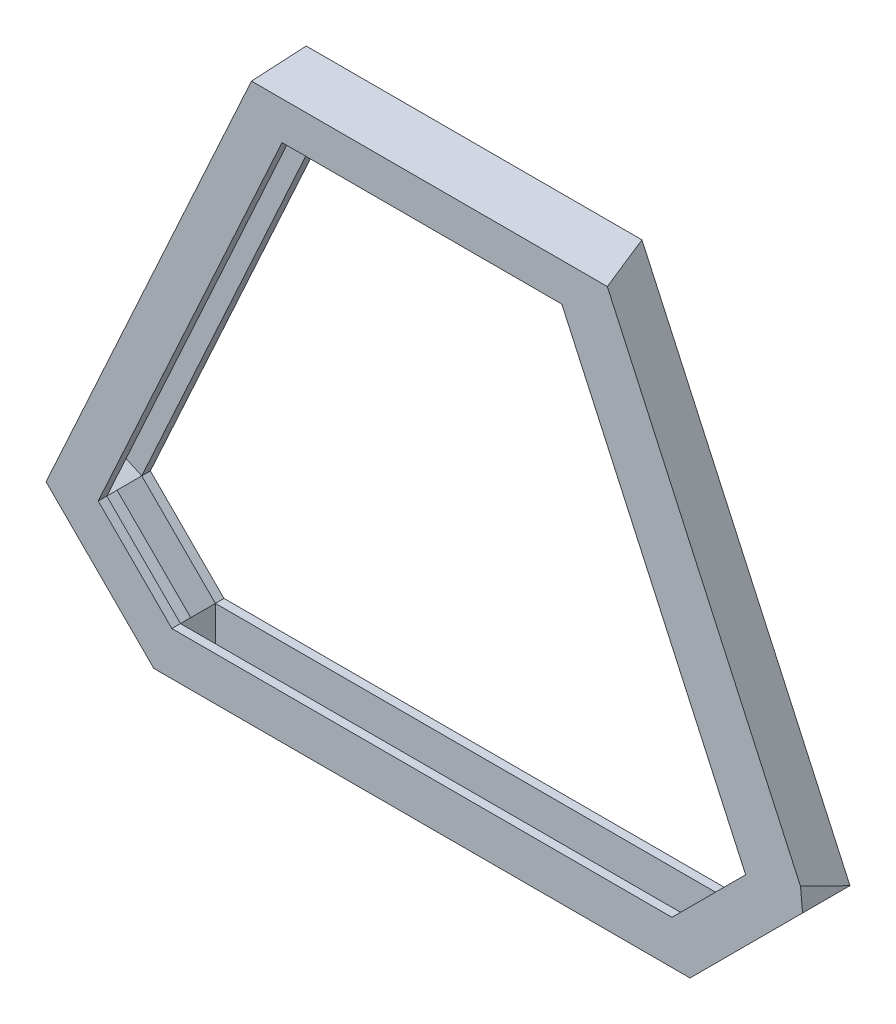
SolidWorks part; units mm, degrees
ref_plane "Front Plane" through (0, 0, 0) normal (0, 0, 1) x (1, 0, 0)
ref_plane "Top Plane" through (0, 0, 0) normal (0, 1, 0) x (1, 0, 0)
ref_plane "Right Plane" through (0, 0, 0) normal (1, 0, 0) x (0, 0, -1)
sketch "Sketch1" plane through (0, 0, 0) normal (0, 0, 1) x (1, 0, 0)
  line L0 (0, -264.5165) -> (-62.614, -327.1305)
  line L1 (-62.614, -327.1305) -> (-374.1336, -327.1305)
  line L2 (-374.1336, -327.1305) -> (-436.7476, -264.5165)
  line L3 (-436.7476, -264.5165) -> (-315.9032, 0)
  line L4 (-315.9032, 0) -> (-120.8445, 0)
  line L5 (-120.8445, 0) -> (0, -264.5165)
extrude "Boss-Extrude1" add sketch "Sketch1" along normal blind 5
sketch "Sketch2" plane through (0, 0, 5) normal (0, 0, 1) x (1, 0, 0)
  line L0 (-315.9032, 0) -> (-436.7476, -264.5165) construction
  line L1 (-436.7476, -264.5165) -> (-374.1336, -327.1305) construction
  line L2 (-374.1336, -327.1305) -> (-62.614, -327.1305) construction
  line L3 (-62.614, -327.1305) -> (0, -264.5165) construction
  line L4 (0, -264.5165) -> (-120.8445, 0) construction
  line L5 (-120.8445, 0) -> (-315.9032, 0) construction
  line L6 (-374.1336, -327.1305) -> (-370.5981, -323.595) construction
  line L7 (-436.7476, -264.5165) -> (-433.2121, -260.981) construction
  line L8 (-315.9032, 0) -> (-311.3553, -2.0777) construction
  line L9 (-436.7476, -264.5165) -> (-432.1998, -266.5942) construction
  line L10 (-315.9032, 0) -> (-315.9032, -5) construction
  line L11 (-120.8445, 0) -> (-120.8445, -5) construction
  line L12 (-120.8445, 0) -> (-125.3924, -2.0777) construction
  line L13 (0, -264.5165) -> (-4.5479, -266.5942) construction
  line L14 (-374.1336, -327.1305) -> (-374.1336, -322.1305) construction
  line L15 (-62.614, -327.1305) -> (-62.614, -322.1305) construction
  line L16 (-62.614, -327.1305) -> (-66.1495, -323.595) construction
  line L17 (0, -264.5165) -> (-3.5355, -260.981) construction
  line L18 (-433.2121, -260.981) -> (-370.5981, -323.595) construction
  line L19 (-374.1336, -322.1305) -> (-62.614, -322.1305) construction
  line L20 (-3.5355, -260.981) -> (-66.1495, -323.595) construction
  line L21 (-125.3924, -2.0777) -> (-4.5479, -266.5942) construction
  line L22 (-120.8445, -5) -> (-315.9032, -5) construction
  line L23 (-311.3553, -2.0777) -> (-432.1998, -266.5942) construction
  line L24 (-311.3553, -2.0777) -> (-292.8909, -10.5132) construction
  line L25 (-315.9032, -5) -> (-315.9032, -25.3) construction
  line L26 (-433.2121, -260.981) -> (-418.8578, -246.6267) construction
  line L27 (-432.1998, -266.5942) -> (-413.7354, -275.0297) construction
  line L28 (-374.1336, -322.1305) -> (-374.1336, -301.8305) construction
  line L29 (-370.5981, -323.595) -> (-356.2438, -309.2407) construction
  line L30 (-66.1495, -323.595) -> (-80.5038, -309.2407) construction
  line L31 (-62.614, -322.1305) -> (-62.614, -301.8305) construction
  line L32 (-4.5479, -266.5942) -> (-23.0122, -275.0297) construction
  line L33 (-3.5355, -260.981) -> (-17.8898, -246.6267) construction
  line L34 (-120.8445, -5) -> (-120.8445, -25.3) construction
  line L35 (-125.3924, -2.0777) -> (-143.8567, -10.5132) construction
  line L36 (-315.9032, -25.3) -> (-120.8445, -25.3) construction
  line L37 (-143.8567, -10.5132) -> (-23.0122, -275.0297) construction
  line L38 (-17.8898, -246.6267) -> (-80.5038, -309.2407) construction
  line L39 (-62.614, -301.8305) -> (-374.1336, -301.8305) construction
  line L40 (-356.2438, -309.2407) -> (-418.8578, -246.6267) construction
  line L41 (-413.7354, -275.0297) -> (-292.8909, -10.5132) construction
sketch "Sketch3" plane through (0, 0, 5) normal (0, 0, 1) x (1, 0, 0)
  line L7 (-137.1013, -25.3) -> (-299.6463, -25.3)
  line L8 (-143.8567, -10.5132) -> (-23.0122, -275.0297) construction
  line L9 (-413.7354, -275.0297) -> (-292.8909, -10.5132) construction
  line L10 (-315.9032, -25.3) -> (-120.8445, -25.3) construction
  line L11 (-137.1013, -25.3) -> (-30.3127, -259.0496)
  line L12 (-17.8898, -246.6267) -> (-80.5038, -309.2407) construction
  line L13 (-30.3127, -259.0496) -> (-73.0936, -301.8305)
  line L14 (-299.6463, -25.3) -> (-406.4349, -259.0496)
  line L15 (-356.2438, -309.2407) -> (-418.8578, -246.6267) construction
  line L16 (-62.614, -301.8305) -> (-374.1336, -301.8305) construction
  line L17 (-406.4349, -259.0496) -> (-363.654, -301.8305)
  line L18 (-73.0936, -301.8305) -> (-363.654, -301.8305)
extrude "Cut-Extrude1" cut sketch "Sketch3" against normal through all
sketch "Sketch4" plane through (0, 0, 5) normal (0, 0, 1) x (1, 0, 0)
  line L0 (-312.6903, -5) -> (-124.0573, -5)
  line L1 (-120.8445, -5) -> (-315.9032, -5) construction
  line L2 (-311.3553, -2.0777) -> (-432.1998, -266.5942) construction
  line L3 (-125.3924, -2.0777) -> (-4.5479, -266.5942) construction
  line L4 (-312.6903, -5) -> (-430.757, -263.4361)
  line L5 (-433.2121, -260.981) -> (-370.5981, -323.595) construction
  line L6 (-430.757, -263.4361) -> (-372.0626, -322.1305)
  line L11 (-374.1336, -322.1305) -> (-62.614, -322.1305) construction
  line L12 (-372.0626, -322.1305) -> (-64.6851, -322.1305)
  line L13 (-3.5355, -260.981) -> (-66.1495, -323.595) construction
  line L14 (-64.6851, -322.1305) -> (-5.9907, -263.4361)
  line L15 (-5.9907, -263.4361) -> (-124.0573, -5)
  line L16 (-315.9032, 0) -> (-120.8445, 0)
  line L17 (-315.9032, 0) -> (-436.7476, -264.5165)
  line L18 (-436.7476, -264.5165) -> (-374.1336, -327.1305)
  line L19 (-374.1336, -327.1305) -> (-62.614, -327.1305)
  line L20 (-62.614, -327.1305) -> (0, -264.5165)
  line L21 (0, -264.5165) -> (-120.8445, 0)
extrude "Boss-Extrude3" add sketch "Sketch4" along normal blind 20.3
sketch "Sketch5" plane through (0, 0, 5) normal (0, 0, 1) x (1, 0, 0)
  line L0 (-299.6463, -25.3) -> (-318.1107, -16.8645)
  line L1 (-312.6903, -5) -> (-430.757, -263.4361) construction
  line L2 (-299.6463, -25.3) -> (-299.6463, -5)
  line L3 (-124.0573, -5) -> (-312.6903, -5) construction
  line L4 (-137.1013, -25.3) -> (-137.1013, -5)
  line L5 (-137.1013, -25.3) -> (-118.637, -16.8645)
  line L6 (-5.9907, -263.4361) -> (-124.0573, -5) construction
  line L7 (-406.4349, -259.0496) -> (-424.8993, -250.6142)
  line L8 (-406.4349, -259.0496) -> (-420.7892, -273.4039)
  line L9 (-430.757, -263.4361) -> (-372.0626, -322.1305) construction
  line L10 (-363.654, -301.8305) -> (-378.0083, -316.1848)
  line L11 (-363.654, -301.8305) -> (-363.654, -322.1305)
  line L12 (-372.0626, -322.1305) -> (-64.6851, -322.1305) construction
  line L13 (-372.0626, -322.1305) -> (-64.6851, -322.1305) construction
  line L14 (-73.0936, -301.8305) -> (-73.0936, -322.1305)
  line L15 (-73.0936, -301.8305) -> (-58.7393, -316.1848)
  line L16 (-64.6851, -322.1305) -> (-5.9907, -263.4361) construction
  line L17 (-30.3127, -259.0496) -> (-15.9585, -273.4039)
  line L18 (-30.3127, -259.0496) -> (-11.8484, -250.6142)
  line L19 (-312.6903, -5) -> (-318.1107, -16.8645)
  line L20 (-312.6903, -5) -> (-299.6463, -5)
  line L21 (-137.1013, -5) -> (-124.0573, -5)
  line L22 (-124.0573, -5) -> (-118.637, -16.8645)
  line L23 (-424.8993, -250.6142) -> (-430.757, -263.4361)
  line L24 (-430.757, -263.4361) -> (-420.7892, -273.4039)
  line L25 (-378.0083, -316.1848) -> (-372.0626, -322.1305)
  line L26 (-372.0626, -322.1305) -> (-363.654, -322.1305)
  line L27 (-73.0936, -322.1305) -> (-64.6851, -322.1305)
  line L28 (-58.7393, -316.1848) -> (-64.6851, -322.1305)
  line L29 (-11.8484, -250.6142) -> (-5.9907, -263.4361)
  line L30 (-5.9907, -263.4361) -> (-15.9585, -273.4039)
extrude "Boss-Extrude4" add sketch "Sketch5" along normal up to surface (20.3 mm away) up to face at (-218.3738, -197.2157, 25.3)
sketch "Sketch6" plane through (0, 0, 25.3) normal (0, 0, 1) x (1, 0, 0)
  line L0 (-315.9032, 0) -> (-120.8445, 0)
  line L1 (-120.8445, 0) -> (0, -264.5165)
  line L2 (0, -264.5165) -> (-62.614, -327.1305)
  line L3 (-62.614, -327.1305) -> (-374.1336, -327.1305)
  line L4 (-374.1336, -327.1305) -> (-436.7476, -264.5165)
  line L5 (-436.7476, -264.5165) -> (-315.9032, 0)
  line L6 (-299.6463, -25.3) -> (-406.4349, -259.0496)
  line L7 (-406.4349, -259.0496) -> (-363.654, -301.8305)
  line L8 (-406.4349, -259.0496) -> (-363.654, -301.8305) construction
  line L9 (-363.654, -301.8305) -> (-378.0083, -316.1848) construction
  line L10 (-363.654, -301.8305) -> (-73.0936, -301.8305)
  line L11 (-73.0936, -301.8305) -> (-30.3127, -259.0496)
  line L12 (-30.3127, -259.0496) -> (-137.1013, -25.3)
  line L13 (-137.1013, -25.3) -> (-299.6463, -25.3)
extrude "Boss-Extrude5" add sketch "Sketch6" along normal blind 5
sketch "Sketch7" plane through (-261.3551, 119.4002, 0) normal (-0.9096, 0.4155, 0) x (0, 0, 1)
  line L0 (30.3, -134.8511) -> (30.3, -131.2703)
  line L1 (30.3, -131.2703) -> (30.3, -422.0836) construction
  line L2 (30.3, -131.2703) -> (0, -131.2703)
  line L3 (0, -131.2703) -> (30.3, -134.8511)
  point P5 (0, 0)
sketch "Sketch8" plane through (0, 0, 30.3) normal (0, 0, 1) x (1, 0, 0)
  line L0 (-317.3911, -3.257) -> (-119.3565, -3.257)
  line L1 (0, -264.5165) -> (-120.8445, 0) construction
  line L2 (-120.8445, 0) -> (-315.9032, 0) construction
  point P7 (0, 0)
  point P8 (0, 0)
  point P9 (0, 0)
  point P10 (0, 0)
sketch "Sketch9" plane through (-99.9779, -45.6749, 0) normal (0.9096, 0.4155, 0) x (0, 0, -1)
  line L0 (-30.3, 46.6349) -> (0, 50.2157)
  line L1 (0, -240.5976) -> (0, 50.2157) construction
  line L2 (0, 50.2157) -> (-30.3, 50.2157)
  line L3 (-30.3, 50.2157) -> (0, 50.2157) construction
  line L4 (-30.3, -240.5976) -> (-30.3, 50.2157) construction
  line L5 (-30.3, 46.6349) -> (-30.3, 50.2157)
sketch "Sketch10" plane through (0, 0, 0) normal (0, 1, 0) x (1, 0, 0)
  line L0 (-315.9032, 0) -> (-315.9032, -30.3)
  line L1 (-315.9032, -30.3) -> (-120.8445, -30.3)
  line L2 (-120.8445, -30.3) -> (-120.8445, 0)
  line L3 (-120.8445, 0) -> (-315.9032, 0)
extrude "Cut-Extrude2" cut sketch "Sketch9" along direction (1, 0, 0) on the side against the normal up to vertex (180.1273 mm away) contours L0 L2 L5 up to point (-317.3911, -3.257, 30.3)
sketch "Sketch11" plane through (0, 0, 0) normal (0, 0.9943, 0.1069) x (1, 0, 0)
  line L0 (-120.8445, 0) -> (-119.3565, -30.4745)
  line L1 (-119.3565, -30.4745) -> (-110.6598, -30.4745)
  line L2 (-110.6598, -30.4745) -> (-120.8445, 0)
extrude "Boss-Extrude6" add sketch "Sketch11" along direction (-0.4155, 0.9096, 0) on the side against the normal up to surface (287.2325 mm away) up to face at (-31.307, -295.8235, 15.15)
sketch "Sketch12" plane through (0, 0, 30.3) normal (0, 0, 1) x (1, 0, 0)
  line L0 (5.9696, -258.5469) -> (2.7877, -261.7288)
  line L1 (-62.614, -327.1305) -> (5.9696, -258.5469) construction
  line L2 (2.7877, -261.7288) -> (1.5543, -248.8823)
  line L3 (5.9696, -258.5469) -> (-110.6598, -3.257) construction
  line L4 (1.5543, -248.8823) -> (5.9696, -258.5469)
sketch "Sketch13" plane through (-93.5985, -42.7605, 26.8648) normal (0.8801, 0.4021, -0.2526) x (-0.2298, -0.105, -0.9676)
  line L0 (-3.5503, -237.6484) -> (27.7653, -240.5976)
  line L1 (-3.5503, -227.023) -> (27.7653, -240.5976)
  line L2 (-3.5503, -227.023) -> (-3.5503, -237.6484)
sketch "Sketch15" plane through (132.2582, -132.2582, 0) normal (0.7071, -0.7071, 0) x (0, 0, -1)
  line L0 (-30.3, -183.099) -> (0, -187.0414)
  line L1 (-30.3, -183.099) -> (-30.3, -178.5992)
  line L2 (-30.3, -178.5992) -> (0, -187.0414)
  point P4 (0, 0)
extrude "Cut-Extrude3" cut sketch "Sketch12" along direction (-0.0455, -0.4581, -0.8878) on the side against the normal up to vertex (30.3 mm away) up to point (0, -264.5165, 0)
